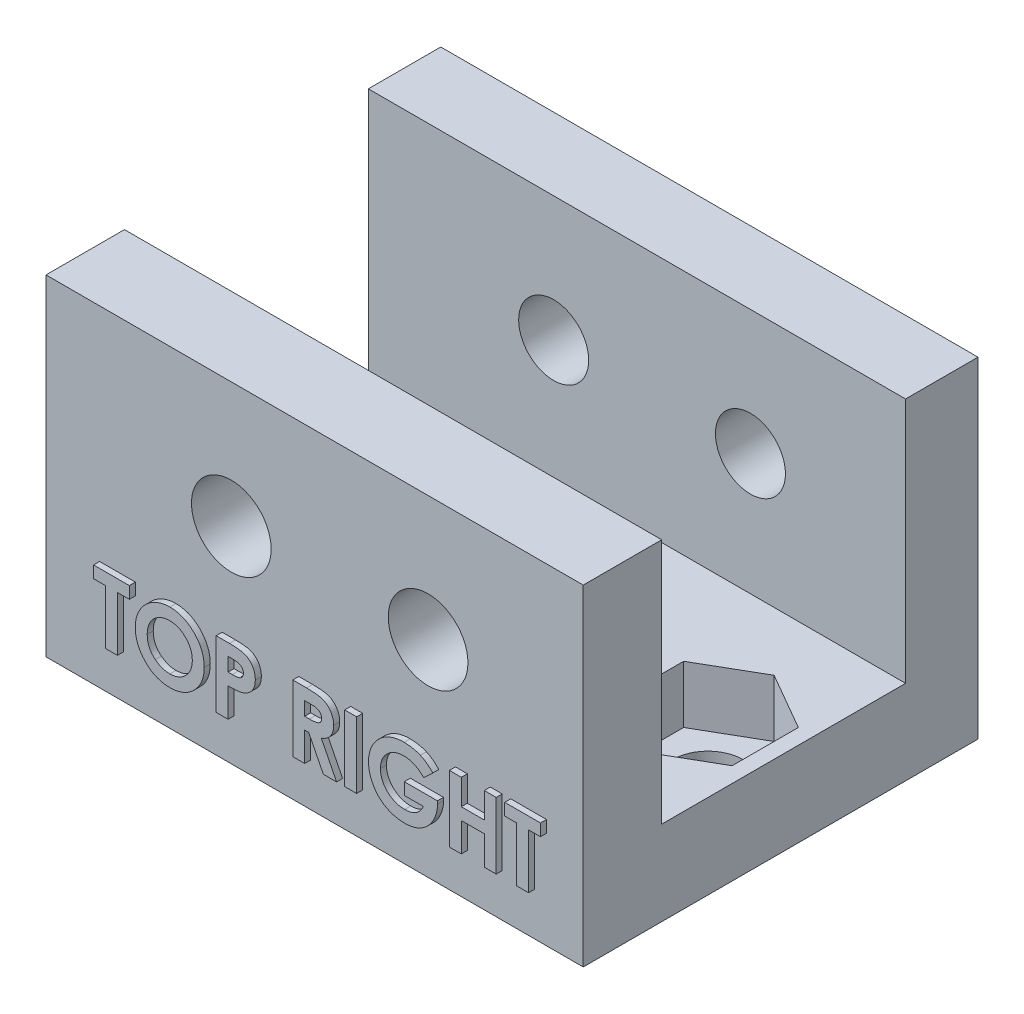
SolidWorks part; units mm, degrees
note: The reader was unsure of these and kept them because the rebuilt part matched: shared geometry of "Sketch2<3>".
material "PA12CF"
ref_plane "Płaszczyzna przednia" through (0, 0, 0) normal (0, 0, 1) x (1, 0, 0)
ref_plane "Płaszczyzna górna" through (0, 0, 0) normal (0, 1, 0) x (1, 0, 0)
ref_plane "Płaszczyzna prawa" through (0, 0, 0) normal (1, 0, 0) x (0, 0, -1)
sketch "Sketch1" plane through (0, 0, 0) normal (0, 0, 1) x (1, 0, 0)
  line L3 (-14.75, 10) -> (29.75, 10)
  line L4 (-14.75, 10) -> (-14.75, -10)
  line L5 (-14.75, -10) -> (29.75, -10)
  line L6 (29.75, 10) -> (29.75, -10)
  dimension "D5" = 20
extrude "Boss-Extrude1" add sketch "Sketch1" along normal blind 6
sketch "Sketch2" plane through (0, 0, 6) normal (0, 0, 1) x (1, 0, 0)
  line L0 (29.75, -10) -> (29.75, 10) construction
  line L1 (-14.75, -10) -> (29.75, -10)
  line L2 (-14.75, -10) -> (-14.75, -17.4)
  line L3 (-14.75, -17.4) -> (29.75, -17.4)
  line L4 (29.75, -10) -> (29.75, -17.4)
  line L6 (-14.75, -17.4) -> (29.75, -17.4)
  line L7 (-14.75, -17.4) -> (-14.75, -10.4)
  line L8 (-14.75, -10.4) -> (29.75, -10.4)
  line L9 (29.75, -17.4) -> (29.75, -10.4)
  line M7 (-14.75, -10) -> (29.75, -10)
  dimension "D1" = 7.4
  dimension "D2" = 7
extrude "Boss-Extrude2" add sketch "Sketch2" against normal blind 6 contours L2 L8 L4 M7 | L8 L2 L3 L4
extrude "Boss-Extrude3" add sketch "Sketch2<3>" along normal blind 20.2 contours L8 L2 L3 L4
sketch "Sketch2<3>" plane through (0, 0, 6) normal (0, 0, 1) x (1, 0, 0) same geometry as "Sketch2"
sketch "Sketch3" plane through (0, 0, 26.2) normal (0, 0, 1) x (1, 0, 0)
  line L4 (-14.75, 10) -> (-14.75, -10.4)
  line L5 (-14.75, -10.4) -> (29.75, -10.4)
  line L6 (29.75, -10.4) -> (29.75, 10)
  line L7 (29.75, 10) -> (-14.75, 10)
  line L8 (-14.75, 10) -> (-14.75, -10.4)
  line L10 (29.75, -10.4) -> (29.75, 10)
  line L11 (29.75, 10) -> (-14.75, 10)
  line L12 (29.75, -10.4) -> (-14.75, -10.4)
  line L13 (-14.75, -10.4) -> (-14.75, -17.4)
  line L14 (-14.75, -17.4) -> (29.75, -17.4)
  line L15 (29.75, -17.4) -> (29.75, -10.4)
  line L17 (-14.75, -10.4) -> (-14.75, -17.4)
  line L18 (-14.75, -17.4) -> (29.75, -17.4)
  line L19 (29.75, -17.4) -> (29.75, -10.4)
  dimension "D1" = 0
  dimension "D2" = 0
extrude "Boss-Extrude4" add sketch "Sketch3" along normal blind 6.5
sketch "Sketch4" plane through (0, -17.4, 0) normal (0, -1, 0) x (1, 0, 0)
  line L0 (-14.75, 0) -> (29.75, 0) construction
  line L1 (-2.7, 0) -> (17.7, 0) construction
  line L2 (-2.7, 0) -> (-2.7, 32.7) construction
  line L3 (-2.7, 32.7) -> (17.7, 32.7) construction
  line L4 (17.7, 0) -> (17.7, 32.7) construction
  line L5 (-14.75, 32.7) -> (29.75, 32.7) construction
  line L6 (-2.7, 32.7) -> (-14.75, 32.7) construction
  line L7 (-8.725, 32.7) -> (-8.725, 16.35) construction
  line L8 (-14.75, 0) -> (-14.75, 32.7) construction
  line L9 (-8.725, 16.35) -> (-14.75, 16.35) construction
  line L10 (7.5, 32.7) -> (7.5, 0) construction
  circle A0 centre (-8.725, 16.35) radius 2.9
  circle A1 centre (23.725, 16.35) radius 2.9
  point P8 (7.5, 32.7)
  point P9 (7.5, 32.7)
  dimension "D2" = 5.8
  dimension "D1" = 20.4
extrude "Cut-Extrude1" cut sketch "Sketch4" against normal through all
sketch "Sketch5" plane through (0, -10.4, 0) normal (0, 1, 0) x (1, 0, 0)
  line L1 (-8.725, -10.8652) -> (-13.475, -13.6076)
  line L2 (-13.475, -13.6076) -> (-13.475, -19.0924)
  line L3 (-13.475, -19.0924) -> (-8.725, -21.8348)
  line L4 (-8.725, -21.8348) -> (-3.975, -19.0924)
  line L5 (-3.975, -19.0924) -> (-3.975, -13.6076)
  line L6 (-3.975, -13.6076) -> (-8.725, -10.8652)
  line L7 (23.725, -10.8652) -> (18.975, -13.6076)
  line L8 (18.975, -13.6076) -> (18.975, -19.0924)
  line L9 (18.975, -19.0924) -> (23.725, -21.8348)
  line L10 (23.725, -21.8348) -> (28.475, -19.0924)
  line L11 (28.475, -19.0924) -> (28.475, -13.6076)
  line L12 (28.475, -13.6076) -> (23.725, -10.8652)
  circle A0 centre (-8.725, -16.35) radius 4.75 construction
  circle A1 centre (23.725, -16.35) radius 4.75 construction
  dimension "D1" = 9.5
extrude "Cut-Extrude2" cut sketch "Sketch5" against normal blind 4.75
sketch "Sketch6" plane through (0, -17.4, 0) normal (0, -1, 0) x (1, 0, 0)
  line L0 (-14.75, 0) -> (29.75, 0) construction
  line L1 (-14.75, 32.7) -> (-2.75, 32.7) construction
  line L2 (-14.75, 32.7) -> (-14.75, 0) construction
  line L3 (-14.75, 0) -> (-2.75, 0) construction
  line L4 (-2.75, 32.7) -> (-2.75, 0) construction
  line L5 (-14.75, 32.7) -> (29.75, 32.7) construction
  line L6 (29.75, 0) -> (17.75, 0) construction
  line L7 (29.75, 0) -> (29.75, 32.7) construction
  line L8 (29.75, 32.7) -> (17.75, 32.7) construction
  line L9 (17.75, 0) -> (17.75, 32.7) construction
  line L10 (29.75, 0) -> (29.75, 32.7) construction
  line L11 (-1.75, 31.7) -> (-1.75, 1)
  line L12 (-2.75, 32.7) -> (17.75, 32.7)
  line L13 (-2.75, 32.7) -> (-2.75, 0)
  line L14 (-2.75, 0) -> (17.75, 0)
  line L15 (17.75, 32.7) -> (17.75, 0)
  line L16 (-1.75, 1) -> (16.75, 1)
  line L17 (16.75, 31.7) -> (16.75, 1)
  line L18 (-1.75, 31.7) -> (16.75, 31.7)
  dimension "D1" = 12
  dimension "D2" = 1
extrude "Cut-Extrude3" cut sketch "Sketch6" against normal blind 0.5 contours L18 L11 L16 L17
chamfer "Chamfer1" [suppressed] distance 5 angle 45
chamfer "Chamfer2" [suppressed] distance 5 angle 45
sketch "Sketch7" [suppressed] plane through (0, 0, 0) normal (0, 0, -1) x (-1, 0, 0)
  text T0 "BOT. RIGHT" font "Century Gothic" height 5.5
sketch "Sketch8" [suppressed] plane through (0, 0, 0) normal (0, 0, -1) x (-1, 0, 0)
  text T0 "BOT. LEFT" font "Century Gothic" height 5.5
extrude "Boss-Extrude5" [suppressed] add sketch "Sketch8" along normal blind 0.5
extrude "Boss-Extrude6" [suppressed] add sketch "Sketch7" along normal blind 0.5
sketch "Sketch9" plane through (0, 0, 32.7) normal (0, 0, 1) x (1, 0, 0)
  text T0 "TOP LEFT" font "Century Gothic" height 5.5
extrude "Boss-Extrude7" [suppressed] add sketch "Sketch9" along normal blind 0.5
sketch "Sketch10" plane through (0, 0, 0) normal (0, 0, -1) x (-1, 0, 0)
  text T0 "THIS SIDE UP" font "Century Gothic" height 5
extrude "Boss-Extrude8" add sketch "Sketch10" along normal blind 0.5
sketch "Sketch11" [suppressed] plane through (0, 0, 32.7) normal (0, 0, 1) x (1, 0, 0)
  text T0 "THIS SIDE UP" font "Century Gothic" height 5
extrude "Boss-Extrude9" [suppressed] add sketch "Sketch11" along normal blind 0.5
hole_wizard "M5 Clearance Hole1" [suppressed] positions "Sketch12" profile "Sketch14" hole size "M5" standard "DIN"
sketch "Sketch12" plane through (0, 0, 0) normal (0, 0, -1) x (-1, 0, 0)
  circle A0 centre (-14.5, 0.8) radius 3 construction
  circle A1 centre (-0.35, -0.3) radius 3 construction
  point P0 (-14.5, 0.8)
  point P2 (-0.35, -0.3)
sketch "Sketch14" plane through (14.5, 0.8, 0) normal (1, 0, 0) x (0, 1, 0)
  line L0 (0, 0) -> (0, 6)
  line L1 (0, 6) -> (2.9, 6)
  line L2 (2.9, 6) -> (2.9, 0)
  line L5 (2.9, 0) -> (0, 0)
  line L11 (0, -6.35) -> (0, 107.95) construction
  dimension "Thru Hole Dia." = 5.8
  dimension "Thru Hole Depth" = 6
sketch "Sketch15" [suppressed] plane through (0, 0, 32.7) normal (0, 0, 1) x (1, 0, 0)
  circle A0 centre (0.35, -0.3) radius 3.3
  circle A1 centre (14.5, 0.8) radius 3.3
  circle A2 centre (0.35, -0.3) radius 2.9 construction
  circle A3 centre (14.5, 0.8) radius 2.9 construction
  dimension "D1" = 6.6
extrude "Cut-Extrude4" [suppressed] cut sketch "Sketch15" against normal up to next and the other way through all
hole_wizard "M5 Clearance Hole2" [suppressed] positions "Sketch16" profile "Sketch17" hole size "M5" standard "DIN"
sketch "Sketch16" plane through (0, 0, 0) normal (0, 0, -1) x (-1, 0, 0)
  circle A0 centre (-13.65, -0.1) radius 3 construction
  circle A1 centre (1.35, -0.4) radius 3 construction
  point P0 (-13.65, -0.1)
  point P2 (1.35, -0.4)
sketch "Sketch17" plane through (13.65, -0.1, 0) normal (1, 0, 0) x (0, 1, 0)
  line L0 (0, 0) -> (0, 6)
  line L1 (0, 6) -> (2.9, 6)
  line L2 (2.9, 6) -> (2.9, 0)
  line L5 (2.9, 0) -> (0, 0)
  line L11 (0, -6.35) -> (0, 107.95) construction
  dimension "Thru Hole Dia." = 5.8
  dimension "Thru Hole Depth" = 6
hole_wizard "Ø6.6 (6.6) Diameter Hole1" [suppressed] positions "Sketch18" profile "Sketch19" hole size "Ø6.6" standard "DIN"
sketch "Sketch18" plane through (0, 0, 32.7) normal (0, 0, 1) x (1, 0, 0)
  circle A0 centre (-1.35, -0.4) radius 2.9 construction
  circle A1 centre (13.65, -0.1) radius 2.9 construction
  point P0 (-1.35, -0.4)
  point P2 (13.65, -0.1)
sketch "Sketch19" plane through (-1.35, -0.4, 32.7) normal (1, 0, 0) x (0, -1, 0)
  line L0 (0, 0) -> (0, 6.5)
  line L1 (0, 6.5) -> (3.3, 6.5)
  line L2 (3.3, 6.5) -> (3.3, 0)
  line L5 (3.3, 0) -> (0, 0)
  line L11 (0, -6.35) -> (0, 107.95) construction
  dimension "Thru Hole Dia." = 6.6
  dimension "Thru Hole Depth" = 6.5
fillet "Fillet1" [suppressed] radius 10
fillet "Fillet2" [suppressed] radius 10
hole_wizard "M5 Clearance Hole3" [suppressed] positions "Sketch20" profile "Sketch21" hole size "M5" standard "DIN"
sketch "Sketch20" plane through (0, 0, 0) normal (0, 0, -1) x (-1, 0, 0)
  circle A0 centre (-15.1, -0.6) radius 3 construction
  circle A2 centre (0.05, -0.6) radius 3 construction
  point P0 (-15.1, -0.6)
  point P2 (0.05, -0.6)
sketch "Sketch21" plane through (15.1, -0.6, 0) normal (1, 0, 0) x (0, 1, 0)
  line L0 (0, 0) -> (0, 6)
  line L1 (0, 6) -> (2.9, 6)
  line L2 (2.9, 6) -> (2.9, 0)
  line L5 (2.9, 0) -> (0, 0)
  line L11 (0, -6.35) -> (0, 107.95) construction
  dimension "Thru Hole Dia." = 5.8
  dimension "Thru Hole Depth" = 6
hole_wizard "Ø6.6 (6.6) Diameter Hole2" [suppressed] positions "Sketch22" profile "Sketch23" hole size "Ø6.6" standard "DIN"
sketch "Sketch22" [suppressed] plane through (0, 0, 32.7) normal (0, 0, 1) x (1, 0, 0)
  circle A0 centre (15.1, -0.6) radius 2.9 construction
  circle A1 centre (-0.05, -0.6) radius 2.9 construction
  point P0 (15.1, -0.6)
  point P2 (-0.05, -0.6)
sketch "Sketch23" plane through (15.1, -0.6, 32.7) normal (1, 0, 0) x (0, -1, 0)
  line L0 (0, 0) -> (0, 6.5)
  line L1 (0, 6.5) -> (3.3, 6.5)
  line L2 (3.3, 6.5) -> (3.3, 0)
  line L5 (3.3, 0) -> (0, 0)
  line L11 (0, -6.35) -> (0, 107.95) construction
  dimension "Thru Hole Dia." = 6.6
  dimension "Thru Hole Depth" = 6.5
sketch "Sketch24" plane through (0, 0, 32.7) normal (0, 0, 1) x (1, 0, 0)
  text T0 "TOP RIGHT" font "Century Gothic" height 5.5
extrude "Boss-Extrude10" add sketch "Sketch24" along normal blind 0.5
hole_wizard "M5 Clearance Hole4" positions "Sketch25" profile "Sketch26" hole size "M5" standard "DIN" end condition up to next
sketch "Sketch25" plane through (0, 0, 0) normal (0, 0, -1) x (-1, 0, 0)
  circle A0 centre (-16.9, -0.35) radius 3 construction
  circle A1 centre (-0.6, -0.35) radius 3 construction
  point P0 (-16.9, -0.35)
  point P2 (-0.6, -0.35)
  point P7 (0, 0)
sketch "Sketch26" plane through (16.9, -0.35, 0) normal (1, 0, 0) x (0, 1, 0)
  line L0 (0, 0) -> (0, 6)
  line L1 (0, 6) -> (2.9, 6)
  line L2 (2.9, 6) -> (2.9, 0)
  line L5 (2.9, 0) -> (0, 0)
  line L11 (0, -6.35) -> (0, 107.95) construction
  dimension "Thru Hole Dia." = 5.8
  dimension "Thru Hole Depth" = 6
hole_wizard "Ø6.6 (6.6) Diameter Hole3" positions "Sketch27" profile "Sketch28" hole size "Ø6.6" standard "DIN" end condition up to next
sketch "Sketch27" plane through (0, 0, 32.7) normal (0, 0, 1) x (1, 0, 0)
  circle A0 centre (0.6, -0.35) radius 2.9 construction
  circle A1 centre (16.9, -0.35) radius 2.9 construction
  point P0 (0.6, -0.35)
  point P2 (16.9, -0.35)
sketch "Sketch28" plane through (0.6, -0.35, 32.7) normal (1, 0, 0) x (0, -1, 0)
  line L0 (0, 0) -> (0, 6.5)
  line L1 (0, 6.5) -> (3.3, 6.5)
  line L2 (3.3, 6.5) -> (3.3, 0)
  line L5 (3.3, 0) -> (0, 0)
  line L11 (0, -6.35) -> (0, 107.95) construction
  dimension "Thru Hole Dia." = 6.6
  dimension "Thru Hole Depth" = 6.5
equation "\"D1@Sketch2\"=\"D2@Sketch2\"+0.4"
